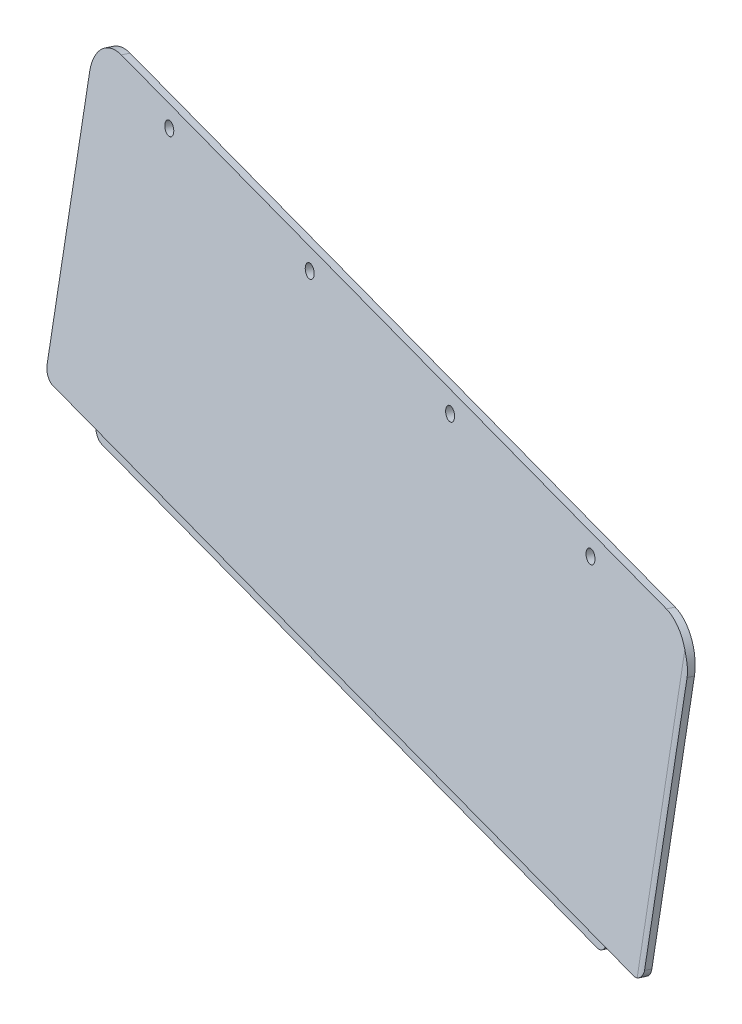
SolidWorks part; units mm, degrees
ref_plane "Front Plane" through (0, 0, 0) normal (0, 0, 1) x (1, 0, 0)
ref_plane "Top Plane" through (0, 0, 0) normal (0, 1, 0) x (1, 0, 0)
ref_plane "Right Plane" through (0, 0, 0) normal (1, 0, 0) x (0, 0, -1)
sketch "Sketch1" plane through (-10.4405, -230.1494, 29.7861) normal (0.0449, 0.9907, -0.1282) x (0.999, -0.0446, 0.0058)
  line L0 (-107.5351, -413.6004) -> (-108.0454, -415.5342) construction
  line L1 (-107.5351, -413.6004) -> (-108.0454, -415.5342)
  line L2 (-108.0454, -415.5342) -> (-104.6421, -416.4323)
  line L4 (-107.5351, -413.6004) -> (-107.6209, -413.9257)
  line L5 (-104.6421, -416.4323) -> (116.1048, -474.6826)
  line L6 (117.8088, -474.7983) -> (118.2367, -473.1767)
  line L7 (118.2367, -473.1767) -> (-107.5351, -413.6004)
  line L8 (-107.5351, -413.6004) -> (-107.6209, -413.9257) construction
  line L9 (-104.6421, -416.4323) -> (116.1048, -474.6826) construction
  line L10 (117.8088, -474.7983) -> (118.2367, -473.1767) construction
  line L11 (118.2367, -473.1767) -> (-107.5351, -413.6004) construction
  ellipse E1 centre (-92.7644, -431.1637) end of major axis (-115.3926, -409.0016) minor radius 2.75 (-104.6421, -416.4323) -> (-107.6209, -413.9257) ccw
  ellipse E2 centre (-92.7644, -431.1637) end of major axis (-115.3926, -409.0016) minor radius 2.75 (-104.6421, -416.4323) -> (-107.6209, -413.9257) ccw construction
  spline S1 degree 3 poles (1281.9328, -5336.5352) (78.6323, -292.5363) (95.817, -473.1758) (139.7548, -476.6215) (180.6502, -277.0979) (-1185.3641, 4350.1229) knots -36.720628 -36.720628 -36.720628 -36.720628 0.5 0.5 40.659731 40.659731 40.659731 40.659731 only from (116.1048, -474.6826) to (117.8088, -474.7983)
  spline S2 degree 3 poles (116.1048, -474.6826) (116.3843, -474.7564) (116.6675, -474.811) (117.2354, -474.8555) (117.5221, -474.8466) (117.8088, -474.7983) knots 0 0 0 0 0.5 0.5 1 1 1 1 construction
  dimension "D1" = 0
extrude "Boss-Extrude1" add sketch "Sketch1" along normal up to surface (81.0627 mm away)
fillet "Fillet1" radius 3 2 edges at (-118.1219, -172.1352, 440.3027)
fillet "Fillet2" radius 10 2 edges at (111.1062, -94.2625, 490.1401) (-114.4786, -91.8242, 429.9088)
sketch "Sketch2" plane through (-108.9256, 57.8948, 409.1578) normal (0.2549, -0.1355, -0.9574) x (-0.967, -0.0357, -0.2524)
  line L0 (-207.7337, -232.2098) -> (-7.9499, -222.914)
  line L1 (-7.9499, -222.914) -> (-7.2992, -236.8989)
  line L2 (-7.2992, -236.8989) -> (-207.083, -246.1946)
  line L3 (-207.083, -246.1946) -> (-207.7337, -232.2098)
  line L4 (-221.0041, -242.838) -> (6.2501, -232.2642) construction
  line L5 (-107.8418, -227.5619) -> (-107.377, -237.5511) construction
  dimension "D1" = 10
  dimension "D2" = 4
  dimension "D3" = 200
extrude "Boss-Extrude2" add sketch "Sketch2" along normal blind 3
fillet "Fillet3" radius 10 3 edges at (-101.463, -167.4904, 443.0359) (91.7222, -169.5601, 494.7584) (-4.6457, -163.5716, 468.256)
fillet "Fillet4" radius 3 4 edges at (91.7, -178.6799, 494.4762) (95.4498, -161.5079, 493.7962) (-104.0495, -159.3705, 440.3833) (-101.4852, -176.6101, 442.7538)
fillet "Fillet5" radius 3 2 edges at (-101.3054, -172.6472, 442.2409) (91.8798, -174.717, 493.9633)
hole_wizard "M3 Clearance Hole1" positions "Sketch3" profile "Sketch4" hole size "M3" standard "ANSI Metric" end condition through all
sketch "Sketch3" plane through (-108.9256, 57.8948, 409.1578) normal (0.2549, -0.1355, -0.9574) x (-0.967, -0.0357, -0.2524)
  line L0 (-189.0777, -165.2075) -> (-24.2561, -157.5385) construction
  line L4 (-217.7793, -161.5375) -> (-4.5101, -151.6144) construction
  line L6 (5.9439, -161.1388) -> (9.1074, -229.128) construction
  point P0 (-189.0777, -165.2075)
  point P2 (-134.1372, -162.6512)
  point P4 (-79.1966, -160.0949)
  point P6 (-24.2561, -157.5385)
  dimension "D1" = 5
  dimension "D2" = 55
  dimension "D3" = 55
  dimension "D4" = 55
  dimension "D5" = 30
sketch "Sketch4" plane through (73.9071, -98.9313, 480.0218) normal (0.7044, 0.7044, 0.0879) x (-0.6625, 0.6968, -0.275)
  line L0 (0, 0) -> (0, 70.4398)
  line L1 (0, 70.4398) -> (1.7, 70.4398)
  line L2 (1.7, 70.4398) -> (1.7, 0.025)
  line L3 (1.7, 0.025) -> (1.725, 0)
  line L5 (1.725, 0) -> (0, 0)
  line L6 (-1.7, 0.025) -> (-1.725, 0) construction
  line L11 (0, -6.35) -> (0, 107.95) construction
  dimension "Thru Hole Dia." = 3.4
  dimension "Thru Hole Depth" = 70.4398
  dimension "Near C'Sink Dia." = 3.45
  dimension "Near C'Sink Angle" = 90
